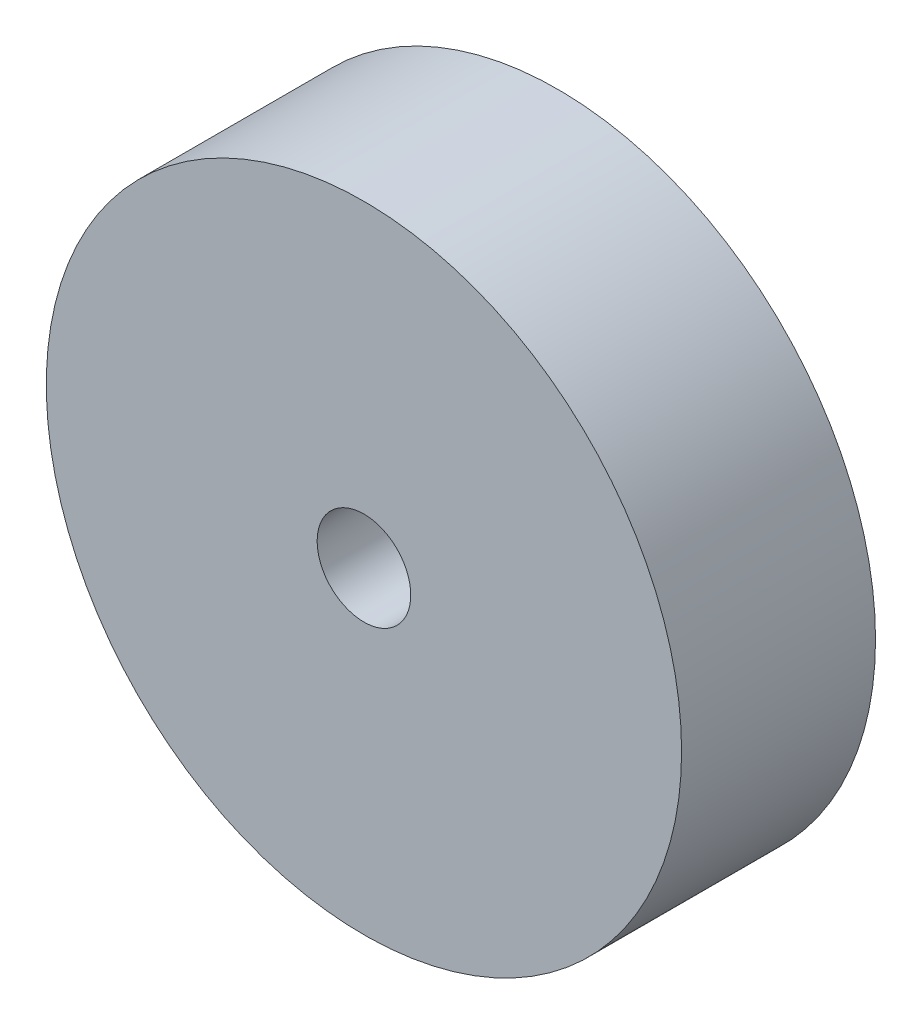
SolidWorks part; units mm, degrees
ref_plane "Front Plane" through (0, 0, 0) normal (0, 0, 1) x (1, 0, 0)
ref_plane "Top Plane" through (0, 0, 0) normal (0, 1, 0) x (1, 0, 0)
ref_plane "Right Plane" through (0, 0, 0) normal (1, 0, 0) x (0, 0, -1)
sketch "Sketch1" plane through (0, 0, 0) normal (0, 0, 1) x (1, 0, 0)
  circle A0 centre (-29.0823, -1.7038) radius 9.5
  dimension "D1" = 19
extrude "Boss-Extrude1" add sketch "Sketch1" along normal blind 5.8
sketch "Sketch2" plane through (0, 0, 0) normal (0, 0, -1) x (-1, 0, 0)
  circle A0 centre (29.0823, -1.7038) radius 7.9
  dimension "D1" = 15.8
extrude "Cut-Extrude1" cut sketch "Sketch2" against normal blind 3.2
sketch "Sketch3" plane through (0, 0, 3.2) normal (0, 0, -1) x (-1, 0, 0)
  circle A0 centre (29.0823, -1.7038) radius 1
  dimension "D1" = 2
extrude "Boss-Extrude2" add sketch "Sketch3" along normal blind 1.5875
sketch "Sketch4" plane through (0, 0, 1.6125) normal (0, 0, -1) x (-1, 0, 0)
  circle A0 centre (29.0823, -1.7038) radius 3.7
  dimension "D1" = 7.4
extrude "Boss-Extrude3" add sketch "Sketch4" against normal blind 3
sketch "Sketch5" plane through (0, 0, 1.6125) normal (0, 0, -1) x (-1, 0, 0)
  circle A0 centre (29.0823, -1.7038) radius 1.4
  dimension "D1" = 2.8
extrude "Cut-Extrude2" cut sketch "Sketch5" against normal through all
chamfer "Chamfer2" distance 1.7 angle 41 1 edges at (-32.7823, -1.7038, 1.6125) first distance on face at (-32.7823, -1.7038, 3.2)
